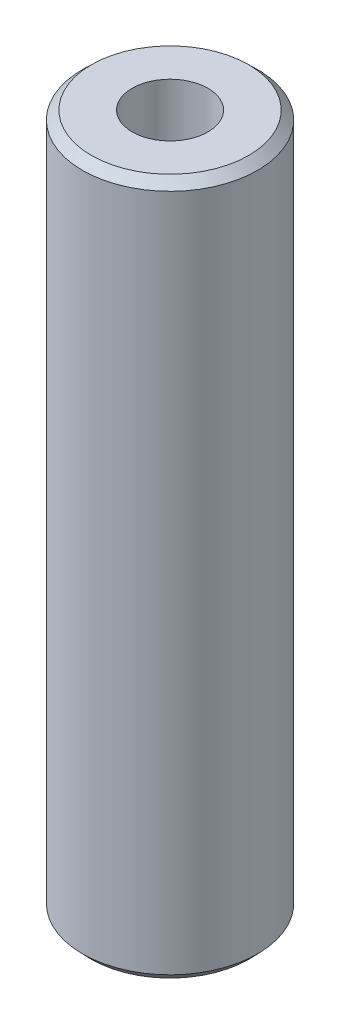
SolidWorks part; units mm, degrees
ref_plane "Front Plane" through (0, 0, 0) normal (0, 0, 1) x (1, 0, 0)
ref_plane "Top Plane" through (0, 0, 0) normal (0, 1, 0) x (1, 0, 0)
ref_plane "Right Plane" through (0, 0, 0) normal (1, 0, 0) x (0, 0, -1)
sketch "Sketch1" plane through (0, 0, 0) normal (0, 1, 0) x (1, 0, 0)
  circle A0 centre (0, 0) radius 40
  dimension "SHAFT_OD" = 80
extrude "Boss-Extrude1" add sketch "Sketch1" along normal blind 318.2334
sketch "Sketch2" plane through (0, 0, 0) normal (0, 1, 0) x (1, 0, 0)
  circle A0 centre (0, 0) radius 17.3096
  dimension "BORE_D" = 34.6191
extrude "Cut-Extrude1" cut sketch "Sketch2" along normal through all
chamfer "Chamfer1" distance 3.8984 angle 46.065 2 edges at (0, 318.2334, 40) (0, 0, 40) first distance on face at (0, 318.2334, 40) first distance on face at (0, 0, 17.3096)
